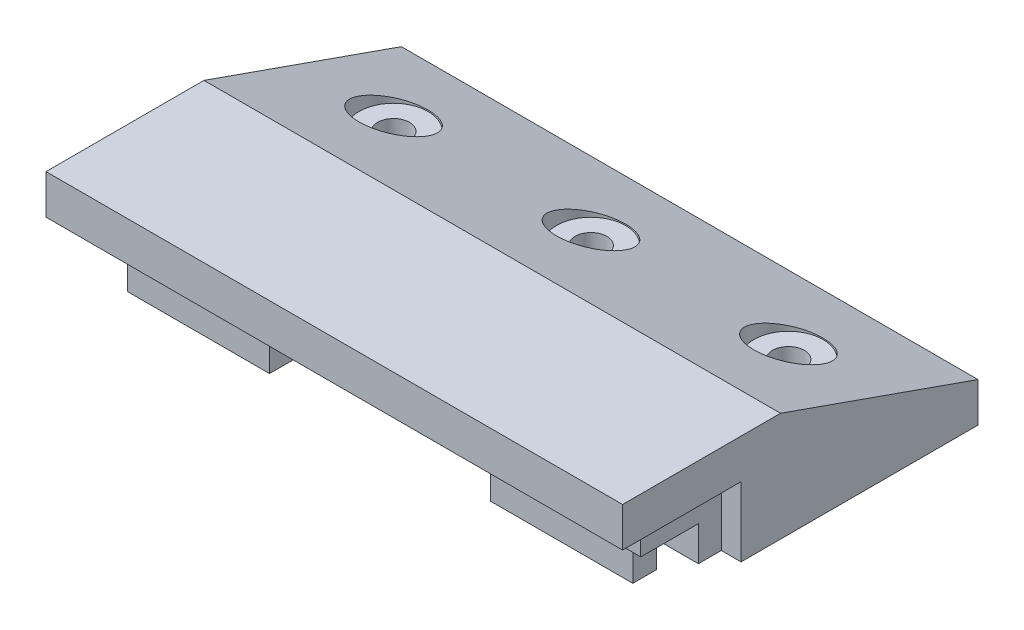
SolidWorks part; units mm, degrees
ref_plane "Front Plane" through (0, 0, 0) normal (0, 0, 1) x (1, 0, 0)
ref_plane "Top Plane" through (0, 0, 0) normal (0, 1, 0) x (1, 0, 0)
ref_plane "Right Plane" through (0, 0, 0) normal (1, 0, 0) x (0, 0, -1)
sketch "Sketch2" plane through (0, 0, 0) normal (1, 0, 0) x (0, 0, -1)
  line L0 (19.05, 0) -> (19.05, -11.176)
  line L1 (0, 0) -> (19.05, 0)
  line L2 (0, 0) -> (0, 6.35)
  line L3 (0, 6.35) -> (25.4, 6.35)
  line L5 (19.05, -11.176) -> (57.15, -11.176)
  line L6 (57.15, -11.176) -> (57.15, -4.826)
  line L7 (57.15, -4.826) -> (25.4, 6.35)
  dimension "D1" = 11.176
  dimension "D2" = 19.05
  dimension "D3" = 6.35
  dimension "D4" = 25.4
  dimension "D5" = 38.1
  dimension "D6" = 6.35
extrude "Boss-Extrude1" add sketch "Sketch2" along normal mid plane 92.71
sketch "Sketch3" plane through (0, 0, 0) normal (0, -1, 0) x (1, 0, 0)
  line L0 (46.355, -19.05) -> (-46.355, -19.05) construction
  line L1 (-43.18, -19.05) -> (43.18, -19.05)
  line L2 (-43.18, -19.05) -> (-43.18, -15.367)
  line L3 (-43.18, -15.367) -> (43.18, -15.367)
  line L4 (43.18, -19.05) -> (43.18, -15.367)
  line L5 (-43.18, -15.367) -> (-43.18, -6.096)
  line L6 (-43.18, -6.096) -> (43.18, -6.096)
  line L7 (43.18, -6.096) -> (43.18, -15.367)
  point P6 (0, -15.367)
  line M6 (-46.355, -19.05) -> (46.355, -19.05)
  dimension "D1" = 3.683
  dimension "D2" = 86.36
  dimension "D3" = 9.271
extrude "Boss-Extrude2" add sketch "Sketch3" along normal up to surface (11.176 mm away) contours L4 L3 L2 M6 region at (0, 0, -17.2085) up to face at (0, -11.176, -38.1)
extrude "Boss-Extrude3" add sketch "Sketch3<3>" along normal offset from surface (5.588 mm away) 5.588 contours L7 L6 L5 L3 region at (0, 0, -10.7315) up to face at (0, -11.176, -27.6543)
sketch "Sketch3<3>" plane through (0, 0, 0) normal (0, -1, 0) x (1, 0, 0) same geometry as "Sketch3"
sketch "Sketch4" plane through (0, -5.588, 0) normal (0, -1, 0) x (1, 0, 0)
  line L0 (-40.64, -7.366) -> (-40.64, -11.176)
  line L3 (-40.64, -11.176) -> (-17.78, -11.176)
  line L4 (-17.78, -11.176) -> (-17.78, -7.366)
  line L5 (-17.78, -7.366) -> (-40.64, -7.366)
  line L6 (0, -9.6393) -> (0, 9.6393) construction
  line L7 (17.78, -11.176) -> (17.78, -7.366)
  line L8 (40.64, -11.176) -> (17.78, -11.176)
  line L9 (40.64, -7.366) -> (40.64, -11.176)
  line L10 (17.78, -7.366) -> (40.64, -7.366)
  line L11 (-43.18, -19.05) -> (-43.18, -6.096) construction
  line L12 (-43.18, -6.096) -> (43.18, -6.096) construction
  dimension "D1" = 2.54
  dimension "D2" = 22.86
  dimension "D3" = 3.81
  dimension "D4" = 1.27
extrude "Boss-Extrude4" add sketch "Sketch4" along normal up to surface (5.588 mm away) up to face at (0, -11.176, -27.6543)
sketch "Sketch7" plane through (0, 6.35, 0) normal (0, -1, 0) x (-1, 0, 0)
  line L0 (0, 9.6393) -> (0, -9.6393) construction
  line L1 (-31.75, 41.275) -> (31.75, 41.275) construction
  line L3 (0, 25.4) -> (0, 57.15) construction
  line L4 (-46.355, 57.15) -> (46.355, 57.15) construction
  line L6 (-46.355, 25.4) -> (46.355, 25.4) construction
  point P0 (-31.75, 41.275)
  point P2 (0, 41.275)
  point P12 (31.75, 41.275)
  point P49 (0, 41.275)
  point P115 (0, 41.275)
  point P118 (0, 0)
  dimension "D1" = 63.5
hole_wizard "CBORE for #10 Binding Head Machine Screw1" positions "Sketch7" profile "Sketch9" counterbore size "#10" standard "ANSI Inch" end condition through all
sketch "Sketch9" plane through (31.75, 6.35, -41.275) normal (1, 0, 0) x (0, 0, 1)
  line L0 (0, 0) -> (0, 17.526)
  line L1 (0, 17.526) -> (2.5527, 17.526)
  line L3 (2.5527, 17.526) -> (2.5527, 7.747)
  line L4 (2.5527, 7.747) -> (5.5562, 7.747)
  line L5 (5.5562, 7.747) -> (5.5562, 0)
  line L7 (5.5562, 0) -> (0, 0)
  line L11 (0, -6.35) -> (0, 107.95) construction
  dimension "Thru Hole Dia." = 5.1054
  dimension "Thru Hole Depth" = 17.526
  dimension "C'Bore Dia." = 11.1125
  dimension "C'Bore Depth" = 7.747
